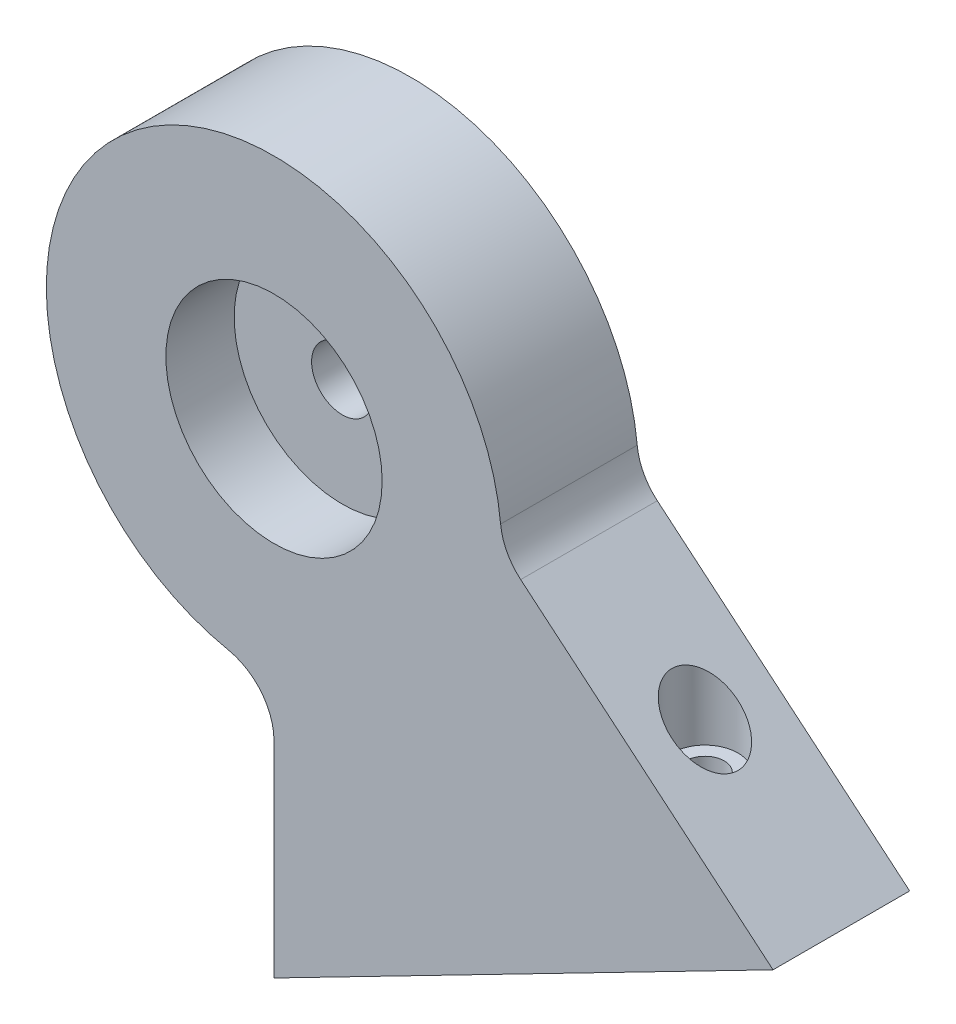
SolidWorks part; units mm, degrees
ref_plane "Front Plane" through (0, 0, 0) normal (0, 0, 1) x (1, 0, 0)
ref_plane "Top Plane" through (0, 0, 0) normal (0, 1, 0) x (1, 0, 0)
ref_plane "Right Plane" through (0, 0, 0) normal (1, 0, 0) x (0, 0, -1)
sketch "Sketch1" plane through (0, 0, 0) normal (0, 0, 1) x (1, 0, 0)
  line L0 (0, 0) -> (0, 80) construction
  line L1 (0, 80) -> (8, 80) construction
  line L3 (20, 80) -> (43.8351, 60)
  line L4 (43.8351, 0) -> (0, 0) construction
  line L5 (0, 60) -> (0, 37.46)
  line L7 (43.8351, 60) -> (43.8351, 0) construction
  line L8 (43.8351, 60) -> (0, 37.46)
  circle A0 centre (0, 80) radius 2.7
  arc A2 (20, 80) -> (0, 60) centre (0, 80) ccw
  dimension "D2" = 5.4
  dimension "D5" = 40
  dimension "D1" = 80
  dimension "D3" = 8
  dimension "D6" = 40
  dimension "D7" = 22.54
extrude "Boss-Extrude1" add sketch "Sketch1" along normal blind 12
ref_plane "Plane1" through (0, 0, 6) normal (0, 0, 1) x (1, 0, 0)
sketch "Sketch4" plane through (0, 0, 6) normal (0, 0, 1) x (1, 0, 0)
  line L0 (0, 48.73) -> (36.1058, 35.5886) construction
  line L1 (0, 60) -> (0, 37.46) construction
  line L2 (0, 51.8161) -> (-0.9919, 49.091)
  line L3 (0, 51.8161) -> (2.8191, 50.7901)
  line L4 (0, 48.73) -> (-17.7647, 55.1958) construction
  line L6 (2.4084, 49.6616) -> (2.8191, 50.7901)
  line L7 (2.4084, 49.6616) -> (23.0816, 42.1372)
  line L8 (23.0816, 42.1372) -> (22.5005, 40.5405)
  line L9 (22.5005, 40.5405) -> (1.8785, 48.0463)
  line L10 (-0.9919, 49.091) -> (1.8785, 48.0463)
  dimension "D1" = 70
  dimension "D2" = 2.9
  dimension "D3" = 3
  dimension "D4" = 1.7
  dimension "D5" = 22
revolve "Cut-Revolve1" cut sketch "Sketch4" angle 360 about L4
sketch "Sketch6" plane through (0, 0, 6) normal (0, 0, 1) x (1, 0, 0)
  line L0 (31.853, 39.1073) -> (31.853, 101.0011) construction
  line L5 (34.753, 66.0542) -> (33.553, 66.0542)
  line L6 (33.553, 66.0542) -> (33.553, 45.0542)
  line L7 (33.553, 45.0542) -> (31.853, 45.0542)
  line L10 (43.8351, 60) -> (20, 80) construction
  line L11 (34.753, 66.0542) -> (34.753, 78.0542)
  line L12 (31.853, 45.0542) -> (31.853, 78.0542)
  line L13 (31.853, 78.0542) -> (34.753, 78.0542)
  point P3 (31.853, 70.0542)
  dimension "D1" = 12
  dimension "D4" = 21
revolve "Cut-Revolve2" cut sketch "Sketch6" angle 360 about L0
fillet "Fillet1" radius 5 2 edges at (20, 80, 6) (0, 60, 6)
sketch "Sketch7" plane through (0, 0, 12) normal (0, 0, 1) x (1, 0, 0)
  circle A0 centre (0, 80) radius 9.5
  dimension "D1" = 19
extrude "Cut-Extrude1" cut sketch "Sketch7" against normal blind 6
